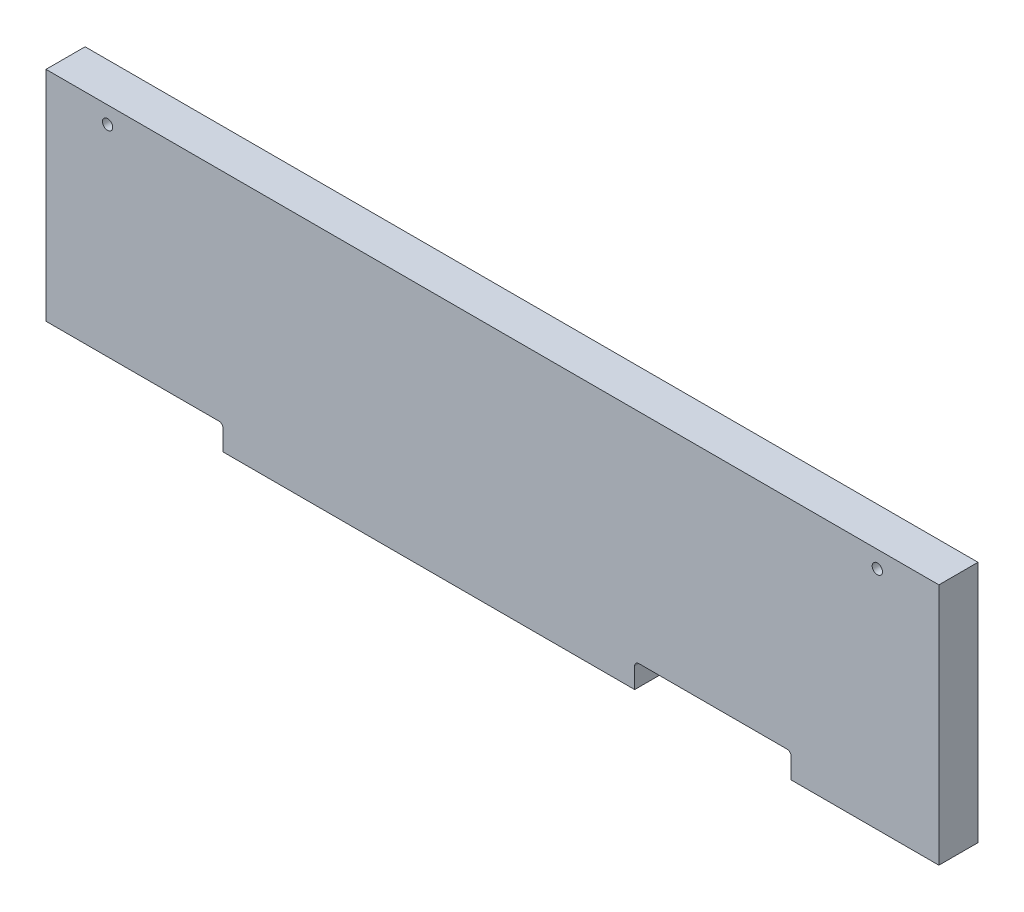
SolidWorks part; units mm, degrees
ref_plane "Front Plane" through (0, 0, 0) normal (0, 0, 1) x (1, 0, 0)
ref_plane "Top Plane" through (0, 0, 0) normal (0, 1, 0) x (1, 0, 0)
ref_plane "Right Plane" through (0, 0, 0) normal (1, 0, 0) x (0, 0, -1)
sketch "Sketch1" plane through (0, 0, 0) normal (0, 0, 1) x (1, 0, 0)
  line L1 (300, 0) -> (-135, 0)
  line L2 (300, 0) -> (300, 118.3)
  line L3 (300, 118.3) -> (-135, 118.3)
  line L4 (-135, 0) -> (-135, 118.3)
  line L5 (-135, 118.3) -> (300, 118.3) construction
  dimension "D1" = 118.3
  dimension "D2" = 435
extrude "Boss-Extrude1" add sketch "Sketch1" along normal blind 19.05
sketch "Sketch2" plane through (0, 0, 19.05) normal (0, 0, 1) x (1, 0, 0)
  line L1 (-48.8, 12) -> (-125, 12) construction
  line L2 (-48.8, 0) -> (-48.8, 12) construction
  line L3 (-135, 0) -> (300, 0) construction
  line L4 (151.8, 0) -> (151.8, 12) construction
  line L5 (151.8, 12) -> (228, 12) construction
  line L6 (228, 12) -> (228, 0) construction
  line L8 (-48.8, 12) -> (-125, 12)
  line L9 (-48.8, 0) -> (-48.8, 12)
  line L10 (-125, 0) -> (-48.8, 0)
  line L11 (151.8, 0) -> (151.8, 12)
  line L12 (151.8, 12) -> (228, 12)
  line L13 (228, 12) -> (228, 0)
  line L14 (151.8, 0) -> (228, 0)
  line L15 (-125, 12) -> (-135, 12)
  line L16 (-135, 118.3) -> (-135, 0) construction
  line L17 (-135, 12) -> (-135, 0)
  line L18 (-135, 0) -> (-125, 0)
extrude "Cut-Extrude1" cut sketch "Sketch2" against normal through all
fillet "Fillet1" radius 2 3 edges at (151.8, 12, 9.525) (228, 12, 9.525) (-48.8, 12, 9.525)
sketch "Sketch3" plane through (0, 0, 0) normal (0, 0, -1) x (-1, 0, 0)
  circle A0 centre (105, 110.05) radius 2.5
  circle A1 centre (-270, 110.05) radius 2.5
extrude "Cut-Extrude2" cut sketch "Sketch3" against normal through all
